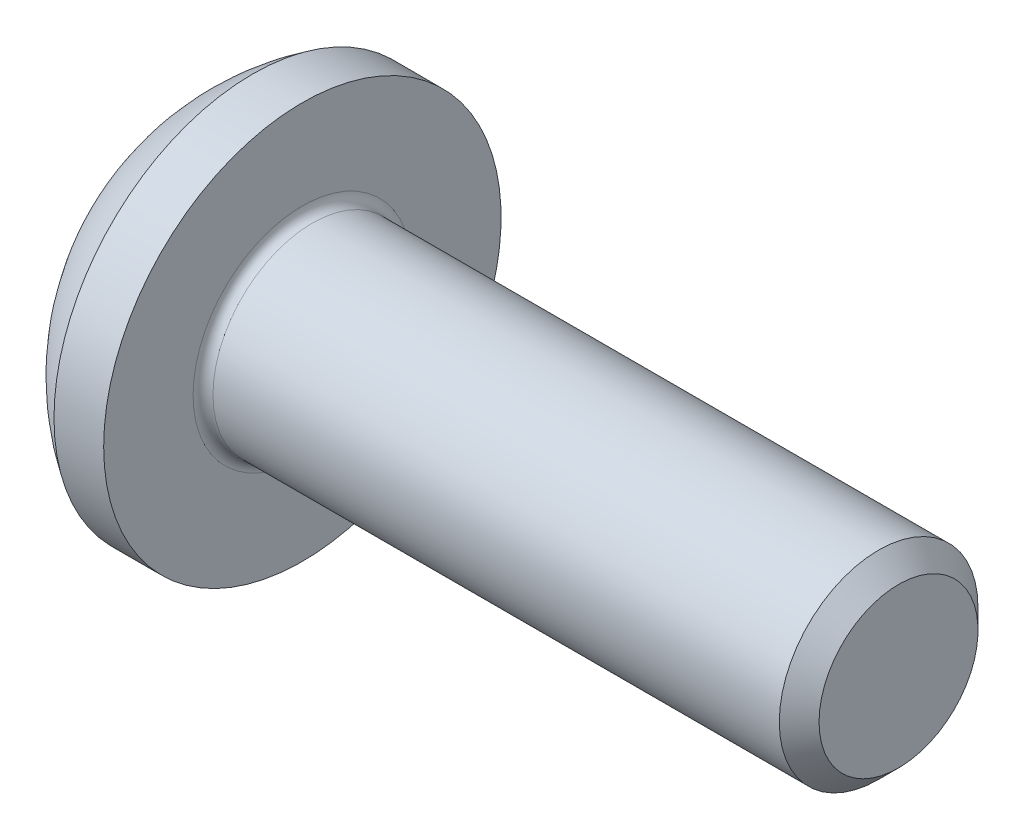
SolidWorks part; units mm, degrees
ref_plane "前视基准面" through (0, 0, 0) normal (0, 0, 1) x (1, 0, 0)
ref_plane "上视基准面" through (0, 0, 0) normal (0, 1, 0) x (1, 0, 0)
ref_plane "右视基准面" through (0, 0, 0) normal (1, 0, 0) x (0, 0, -1)
sketch "草图2" plane through (0, 0, 0) normal (0, 0, 1) x (1, 0, 0)
  line L0 (-1.3318, 0) -> (6.5885, 0) construction
  line L1 (0, 0) -> (7.6, 0)
  line L2 (7.6, 0) -> (7.6, 1)
  line L3 (7.6, 1) -> (1.7, 1)
  line L6 (1.6, 1.1) -> (1.6, 2)
  line L7 (1.6, 2) -> (1.1, 2)
  arc A0 (1.7, 1) -> (1.6, 1.1) centre (1.7, 1.1) cw
  arc A1 (0, 0) -> (1.1, 2) centre (2.3682, 0) cw
  dimension "D3" = 0.5
  dimension "D1" = 0.1
  dimension "d" = 2
  dimension "l" = 6
  dimension "D2" = 2
  dimension "k" = 1.6
revolve "基体-旋转" add sketch "草图2" angle 360 about L0
cosmetic thread "装饰螺纹线1" [suppressed] parameters "D1"=9, "D2"=2.598
sketch "草图5" plane through (0, 0, 0) normal (1, 0, 0) x (0, 0, -1)
  line L1 (0.25, 0.95) -> (-0.25, 0.95)
  line L2 (0.25, 0.95) -> (0.25, -0.95)
  line L3 (0.25, -0.95) -> (-0.25, -0.95)
  line L4 (-0.25, 0.95) -> (-0.25, -0.95)
  point P4 (0.25, 0)
  point P5 (0, 0.95)
  dimension "D1" = 0.5
  dimension "m" = 1.9
ref_plane "基准面12" through (1.2, 0, 0) normal (1, 0, 0) x (0, 0, -1)
sketch "草图6" plane through (1.2, 0, 0) normal (1, 0, 0) x (0, 0, -1)
  point P0 (0, 0)
loft "切除-放样1" cut profiles "草图6", "草图5"
ref_plane "基准面2" through (0, 0, 0) normal (0, -0.7071, 0.7071) x (1, 0, 0)
mirror "镜向1" about plane through (0, 0, 0) normal (0, -0.7071, 0.7071) of "切除-放样1"
ref_axis "基准轴1" through (7.6, 0, 0) along (-1, 0, 0)
ref_plane "基准面3" through (1.6, 0, 0) normal (1, 0, 0) x (0, 0, -1)
chamfer "倒角1" distance 0.2 angle 45 1 edges at (7.6, 0, 1)
ref_plane "基准面1" through (1.6, 0, 0) normal (1, 0, 0) x (0, 0, -1)
